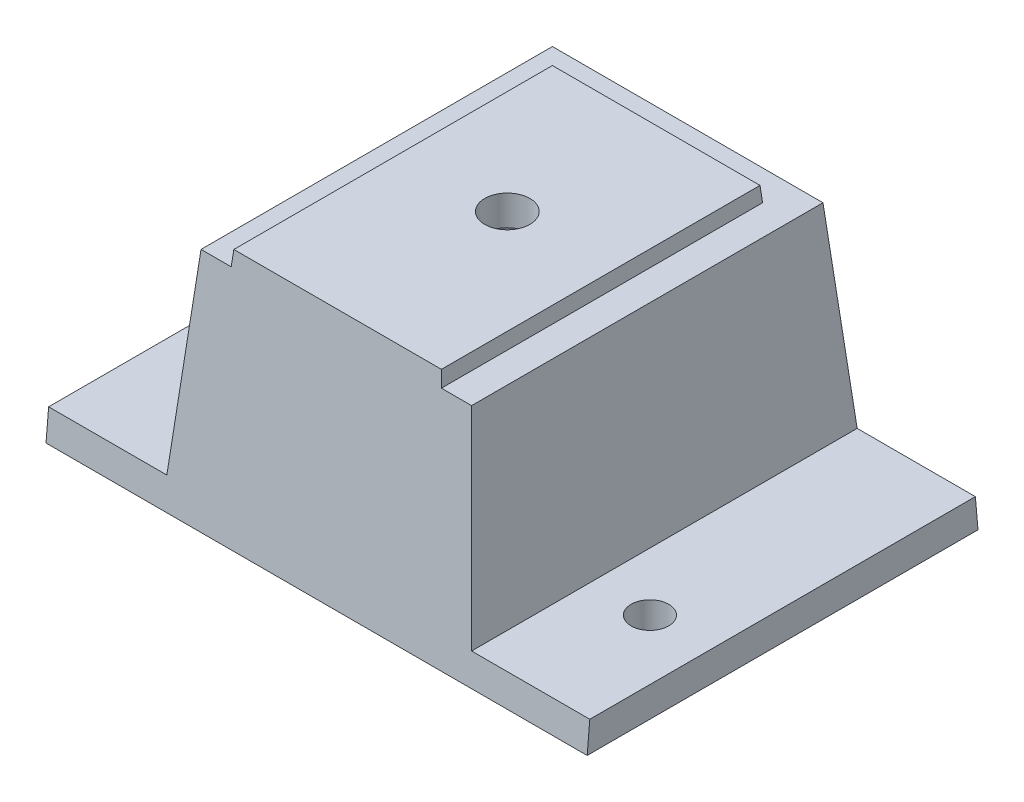
SolidWorks part; units mm, degrees
material "6061 Alloy"
ref_plane "Front Plane" through (0, 0, 0) normal (0, 0, 1) x (1, 0, 0)
ref_plane "Top Plane" through (0, 0, 0) normal (0, 1, 0) x (1, 0, 0)
ref_plane "Right Plane" through (0, 0, 0) normal (1, 0, 0) x (0, 0, -1)
sketch "Sketch1" plane through (0, 0, 0) normal (0, 0, 1) x (1, 0, 0)
  line L0 (0, 0) -> (0, 65.9076) construction
  line L1 (57.15, 0) -> (-57.15, 0)
  line L2 (-57.15, 0) -> (-57.15, 6.35)
  line L3 (-57.15, 6.35) -> (-32.1861, 6.35)
  line L4 (-32.1861, 6.35) -> (-28.575, 47.625)
  line L5 (-21.923, 50.8) -> (21.923, 50.8)
  line L6 (57.15, 0) -> (57.15, 6.35)
  line L7 (57.15, 6.35) -> (32.1861, 6.35)
  line L8 (32.1861, 6.35) -> (28.575, 47.625)
  line L9 (-28.575, 47.625) -> (-22.2007, 47.625)
  line L10 (-22.2007, 47.625) -> (-21.923, 50.8)
  line L11 (21.923, 50.8) -> (22.2007, 47.625)
  line L12 (22.2007, 47.625) -> (28.575, 47.625)
  point P12 (0, 50.8)
  point P15 (-22.0619, 49.2125)
  dimension "D3" = 50.8
  dimension "D4" = 95
  dimension "D6" = 3.175
extrude "Boss-Extrude1" add sketch "Sketch1" along normal blind 82.55
shell "Shell1" thickness 6.35 removed face at (0, 0, 41.275)
ref_plane "Plane1" through (0, 0, 0) normal (0, 0.0872, -0.9962) x (1, 0, 0)
sketch "Sketch4" plane through (0, 0, 0) normal (0, 0.0872, -0.9962) x (1, 0, 0)
  line L1 (100.6752, 17.1493) -> (-75.8106, 17.1493)
  line L2 (100.6752, 17.1493) -> (100.6752, -72.9485)
  line L3 (100.6752, -72.9485) -> (-75.8106, -72.9485)
  line L4 (-75.8106, 17.1493) -> (-75.8106, -72.9485)
extrude "Cut-Extrude1" cut sketch "Sketch4" along normal blind 25.4
sketch "Sketch7" plane through (0, 0, 0) normal (1, 0, 0) x (0, 0, -1)
  line L0 (-4.1666, 47.625) -> (-10.5409, 47.625)
  line L1 (2.7707, -31.6698) -> (-2.7707, 31.6698) construction
  line L2 (-82.55, 47.625) -> (-4.1666, 47.625) construction
  line L3 (-10.5409, 47.625) -> (-10.8187, 50.8)
  line L4 (-82.55, 50.8) -> (-4.4444, 50.8) construction
  line L5 (-10.8187, 50.8) -> (-4.4444, 50.8)
  line L6 (-4.4444, 50.8) -> (-4.1666, 47.625)
  dimension "D1" = 6.35
extrude "Cut-Extrude2" cut sketch "Sketch7" against normal through all both and the other way through all
ref_plane "Plane2" through (0, 0, 82.55) normal (0, 0, 1) x (1, 0, 0)
ref_plane "Plane3" through (0, 0, 41.275) normal (0, 0, 1) x (1, 0, 0)
mirror "Mirror1" about plane through (0, 0, 41.275) normal (0, 0, 1) of "Cut-Extrude1"
sketch "Sketch8" plane through (0, 50.8, 0) normal (0, 1, 0) x (1, 0, 0)
  line L0 (28.575, -4.1666) -> (-28.575, -4.1666) construction
  line L1 (0, 0) -> (0, -42.2666) construction
  line L2 (57.15, -81.9944) -> (57.15, -0.5556) construction
  line L3 (32.1861, -81.9944) -> (57.15, -81.9944) construction
  line L4 (0, -27.94) -> (0, 27.94) construction
  circle A0 centre (0, -42.2666) radius 4.7625
  circle A1 centre (44.45, -56.5944) radius 3.9687
  circle A2 centre (-44.45, -56.5944) radius 3.9687
  dimension "D2" = 9.525
  dimension "D5" = 7.9375
  dimension "D1" = 38.1
  dimension "D3" = 12.7
  dimension "D4" = 25.4
extrude "Cut-Extrude3" cut sketch "Sketch8" against normal through all
equation "\"BedBaseDraftAngle\"=95"
equation "\"D4@Sketch1\"=\"BedBaseDraftAngle\""
